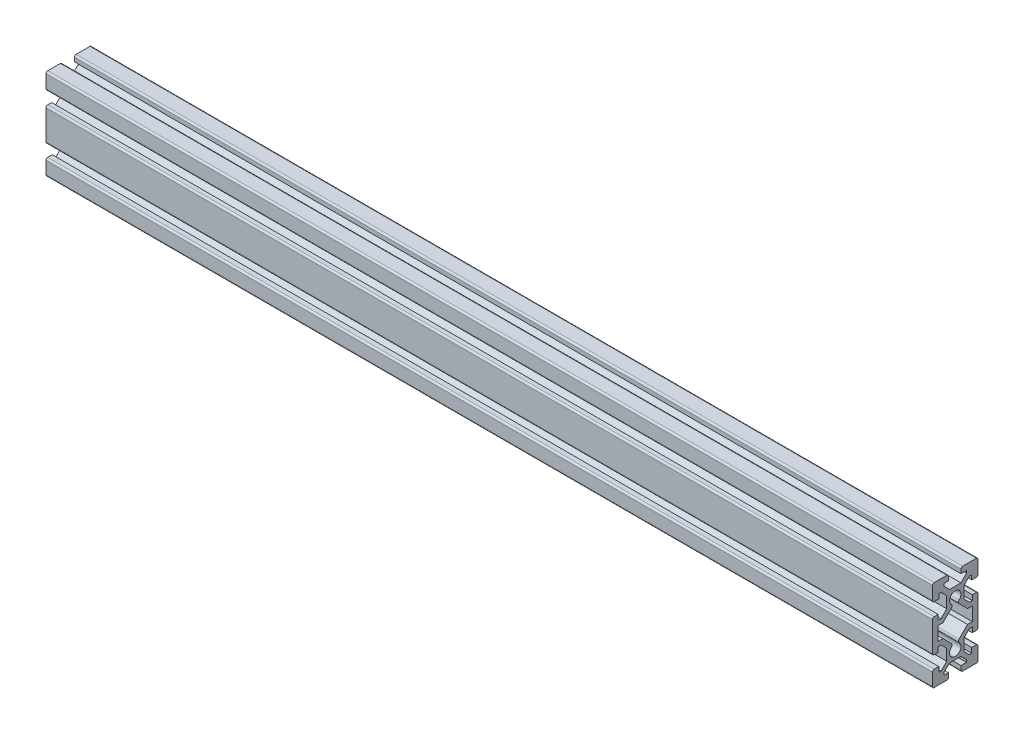
SolidWorks part; units mm, degrees
ref_plane "Piano frontale" through (0, 0, 0) normal (0, 0, 1) x (1, 0, 0)
ref_plane "Piano superiore" through (0, 0, 0) normal (0, 1, 0) x (1, 0, 0)
ref_plane "Piano destro" through (0, 0, 0) normal (1, 0, 0) x (0, 0, -1)
sketch "Schizzo1" plane through (0, 0, 0) normal (1, 0, 0) x (0, 0, -1)
  line L0 (20, 40.5) -> (5, 40.5) construction
  line L1 (18.5, -39.5) -> (6.5, -39.5)
  line L2 (-15, 6.0503) -> (-10.7929, 6.0503)
  line L3 (18.5, 40.5) -> (6.5, 40.5)
  line L4 (-20, -38) -> (-20, -27)
  line L7 (20, -39.5) -> (5, -39.5) construction
  line L21 (-12.4497, 10.0503) -> (-7.5, 15)
  line L22 (-20, -13) -> (-20, 13)
  line L23 (-18.5, 14.5) -> (-15, 14.5)
  line L24 (-14.5, 26) -> (-14.5, 29.9497)
  line L25 (-18.5, 26) -> (-14.5, 26)
  line L26 (-15, 10.0503) -> (-15, 14.5)
  line L27 (-12.4497, 10.0503) -> (-15, 10.0503)
  line L28 (-7.5, 15) -> (-7.5, 25)
  line L29 (-12.4497, 29.9497) -> (-14.5, 29.9497)
  line L30 (-12.4497, 29.9497) -> (-7.5, 25)
  line L32 (-12.4497, -29.9497) -> (-7.5, -25)
  line L33 (-12.4497, -29.9497) -> (-14.5, -29.9497)
  line L34 (-7.5, -15) -> (-7.5, -25)
  line L35 (-12.4497, -10.0503) -> (-15, -10.0503)
  line L36 (-15, -10.0503) -> (-15, -14.5)
  line L37 (-18.5, -25.5) -> (-14.5, -25.5)
  line L38 (-14.5, -25.5) -> (-14.5, -29.9497)
  line L39 (-18.5, -14.5) -> (-15, -14.5)
  line L40 (-9.9497, 35.5) -> (-6, 35.5)
  line L41 (-12.4497, -10.0503) -> (-7.5, -15)
  line L42 (20, -39.5) -> (5, -39.5) construction
  line L43 (-20, 27.5) -> (-20, 39)
  line L44 (-6, 39) -> (-6, 35.5)
  line L45 (5, 39) -> (5, 35.5)
  line L46 (9.9497, 33.4497) -> (5, 28.5)
  line L47 (-5, 28.5) -> (5, 28.5)
  line L48 (5, 35.5) -> (9.9497, 35.5)
  line L49 (-9.9497, 33.4497) -> (-9.9497, 35.5)
  line L50 (-9.9497, 33.4497) -> (-5, 28.5)
  line L51 (9.9497, 33.4497) -> (9.9497, 35.5)
  line L52 (9.9497, -32.4497) -> (9.9497, -34.5)
  line L53 (5, 40.5) -> (0, 40.5) construction
  line L54 (9.9497, 33.4497) -> (9.9497, 35.5)
  line L55 (0, -39.5) -> (5, -39.5) construction
  line L56 (9.9497, -32.4497) -> (9.9497, -34.5)
  line L57 (-9.9497, -32.4497) -> (-5, -27.5)
  line L58 (-9.9497, -32.4497) -> (-9.9497, -34.5)
  line L59 (5, -34.5) -> (9.9497, -34.5)
  line L60 (-5, -27.5) -> (5, -27.5)
  line L61 (9.9497, -32.4497) -> (5, -27.5)
  line L62 (5, -38) -> (5, -34.5)
  line L63 (-6, -38) -> (-6, -34.5)
  line L64 (-9.9497, -34.5) -> (-6, -34.5)
  line L65 (-7.5, 40.5) -> (-18.5, 40.5)
  line L66 (-7.5, -39.5) -> (-18.5, -39.5)
  line L70 (20, 27.5) -> (20, 39)
  line L71 (12.4497, -10.0503) -> (7.5, -15)
  line L72 (18.5, -14.5) -> (15, -14.5)
  line L73 (14.5, -25.5) -> (14.5, -29.9497)
  line L74 (18.5, -25.5) -> (14.5, -25.5)
  line L75 (15, -10.0503) -> (15, -14.5)
  line L76 (12.4497, -10.0503) -> (15, -10.0503)
  line L77 (7.5, -15) -> (7.5, -25)
  line L78 (12.4497, -29.9497) -> (14.5, -29.9497)
  line L79 (12.4497, -29.9497) -> (7.5, -25)
  line L80 (12.4497, 29.9497) -> (7.5, 25)
  line L81 (12.4497, 29.9497) -> (14.5, 29.9497)
  line L82 (7.5, 15) -> (7.5, 25)
  line L83 (12.4497, 10.0503) -> (15, 10.0503)
  line L84 (15, 10.0503) -> (15, 14.5)
  line L85 (18.5, 26) -> (14.5, 26)
  line L86 (14.5, 26) -> (14.5, 29.9497)
  line L87 (18.5, 14.5) -> (15, 14.5)
  line L88 (20, -13) -> (20, 13)
  line L89 (12.4497, 10.0503) -> (7.5, 15)
  line L90 (20, -38) -> (20, -27)
  line L91 (-15, 6.0503) -> (-15, -6.0503)
  line L92 (-15, 10.0503) -> (-15, 10)
  line L93 (-15, -10) -> (-15, -10.0503)
  line L94 (15, 10.0503) -> (15, 10)
  line L95 (-15, -6.0503) -> (-10.7929, -6.0503)
  line L96 (15, -10) -> (15, -10.0503)
  line L97 (15, 6.0503) -> (15, -6.0503)
  line L98 (-10.7929, 6.0503) -> (-3.3686, 13.4746)
  line L99 (10.7929, 6.0503) -> (3.3686, 13.4746)
  line L100 (10.7929, -6.0503) -> (3.3686, -13.4746)
  line L101 (-10.7929, -6.0503) -> (-3.3686, -13.4746)
  line L106 (10.7929, -6.0503) -> (15, -6.0503)
  line L107 (10.7929, 6.0503) -> (15, 6.0503)
  arc A0 (3.4163, 16.3491) -> (-3.4163, 16.3491) centre (0, 20) ccw
  arc A1 (-3.4163, -16.3491) -> (3.4163, -16.3491) centre (0, -20) ccw
  arc A2 (-3.3686, -13.4746) -> (-3.4163, -16.3491) centre (-4.7828, -14.8888) cw
  arc A3 (3.4163, -16.3491) -> (3.3686, -13.4746) centre (4.7828, -14.8888) cw
  arc A4 (3.4163, 16.3491) -> (3.3686, 13.4746) centre (4.7828, 14.8888) ccw
  arc A5 (-3.4163, 16.3491) -> (-3.3686, 13.4746) centre (-4.7828, 14.8888) cw
  arc A6 (-18.5, -25.5) -> (-20, -27) centre (-18.5, -27) ccw
  arc A7 (-7.5, -39.5) -> (-6, -38) centre (-7.5, -38) ccw
  arc A8 (6.5, -39.5) -> (5, -38) centre (6.5, -38) cw
  arc A9 (18.5, -25.5) -> (20, -27) centre (18.5, -27) cw
  arc A10 (20, -38) -> (18.5, -39.5) centre (18.5, -38) cw
  arc A11 (-18.5, -39.5) -> (-20, -38) centre (-18.5, -38) cw
  arc A12 (-20, 39) -> (-18.5, 40.5) centre (-18.5, 39) cw
  arc A13 (6.5, 40.5) -> (5, 39) centre (6.5, 39) ccw
  arc A14 (18.5, 40.5) -> (20, 39) centre (18.5, 39) cw
  arc A15 (20, 27.5) -> (18.5, 26) centre (18.5, 27.5) cw
  arc A16 (18.5, 14.5) -> (20, 13) centre (18.5, 13) cw
  arc A17 (20, -13) -> (18.5, -14.5) centre (18.5, -13) cw
  arc A18 (-18.5, -14.5) -> (-20, -13) centre (-18.5, -13) cw
  arc A19 (-20, 13) -> (-18.5, 14.5) centre (-18.5, 13) cw
  arc A20 (-18.5, 26) -> (-20, 27.5) centre (-18.5, 27.5) cw
  arc A21 (-7.5, 40.5) -> (-6, 39) centre (-7.5, 39) cw
  point P0 (0, 0)
  point P130 (-20, -25.5)
  point P166 (-20, -14.5)
  point P169 (-20, 14.5)
  point P172 (-20, 26)
  point P175 (-6, 40.5)
  dimension "D1" = 5
  dimension "D2" = 1.5
  dimension "D7" = 10
  dimension "D8" = 13.4746
  dimension "D3" = 20
  dimension "D4" = 6
  dimension "D5" = 9.9497
  dimension "D6" = 6.0503
  dimension "D9" = 25
  dimension "D10" = 14.5
  dimension "D11" = 15
  dimension "D12" = 14.5
  dimension "D13" = 25
  dimension "D14" = 29.9497
  dimension "D15" = 2
  dimension "D16" = 16.3491
  dimension "D18" = 26
  dimension "D20" = 14.5
  dimension "D21" = 15
  dimension "D22" = 20
  dimension "D25" = 35.5
  dimension "D28" = 10
  dimension "D37" = 25.5
  dimension "D42" = 39.5
extrude "Estrusione-Estrusione1" add sketch "Schizzo1" along normal blind 780 contours A21 L65 A12 L43 A20 L25 L24 L29 L30 L28 L21 L27 L26 L23 A19 L22 A18 L39 L36 L35 L41 L34 L32 L33 L38 L37 A6 L4 A11 L66 A7 L63 L64 L58 L57 L60 L61 L52 L59 L62 A8 L1 A10 L90 A9 L74 L73 region at (0, -38.6056, -12.5)
sketch "Sketch1" plane through (0, 0, 7.5) normal (0, 0, 1) x (1, 0, 0)
  line L0 (0, 20) -> (780, 20) construction
  line L1 (0, 15) -> (0, 25) construction
  line L2 (780, 15) -> (780, 25) construction
